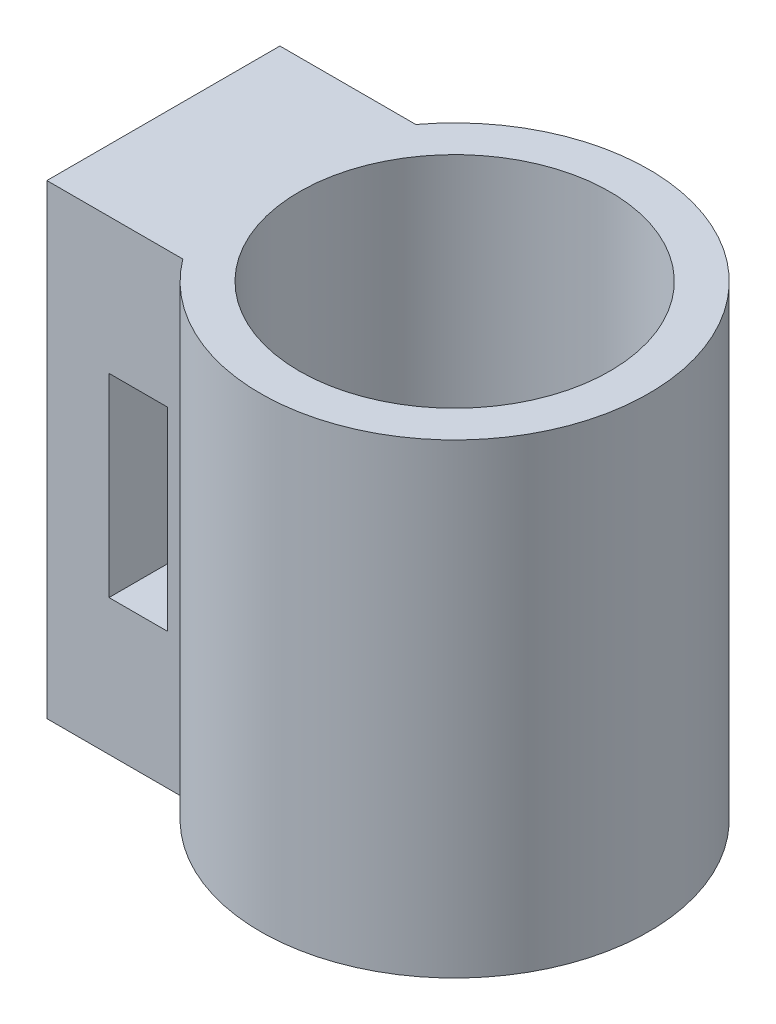
SolidWorks part; units mm, degrees
ref_plane "Front Plane" through (0, 0, 0) normal (0, 0, 1) x (1, 0, 0)
ref_plane "Top Plane" through (0, 0, 0) normal (0, 1, 0) x (1, 0, 0)
ref_plane "Right Plane" through (0, 0, 0) normal (1, 0, 0) x (0, 0, -1)
sketch "Sketch1" plane through (0, 0, 0) normal (0, 1, 0) x (1, 0, 0)
  line L0 (0, 0) -> (-14.5636, 0) construction
  line L1 (-4, 3) -> (-7.5, 3)
  line L2 (-7.5, 3) -> (-7.5, -3)
  line L3 (-4, -3) -> (-7.5, -3)
  circle A0 centre (0, 0) radius 4
  arc A1 (-4, -3) -> (-4, 3) centre (0, 0) ccw
  point P10 (-7.5, 0)
  dimension "D1" = 8
  dimension "D2" = 1
  dimension "D3" = 6
  dimension "D4" = 7.5
extrude "Boss-Extrude1" add sketch "Sketch1" along normal blind 6 and the other way blind 6
sketch "Sketch2" plane through (0, 0, -3) normal (0, 0, -1) x (-1, 0, 0)
  line L0 (-6.9549, 0) -> (16.7857, 0) construction
  line L1 (4.4, -2.5) -> (4.4, 2.5)
  line L2 (4.4, 2.5) -> (5.9, 2.5)
  line L3 (5.9, 2.5) -> (5.9, -2.5)
  line L4 (4.4, -2.5) -> (5.9, -2.5)
  point P8 (5.9, 0)
  point P9 (4.4, 0)
  dimension "D1" = 5
  dimension "D2" = 4.4
  dimension "D3" = 1.5
extrude "Cut-Extrude1" cut sketch "Sketch2" against normal through all
